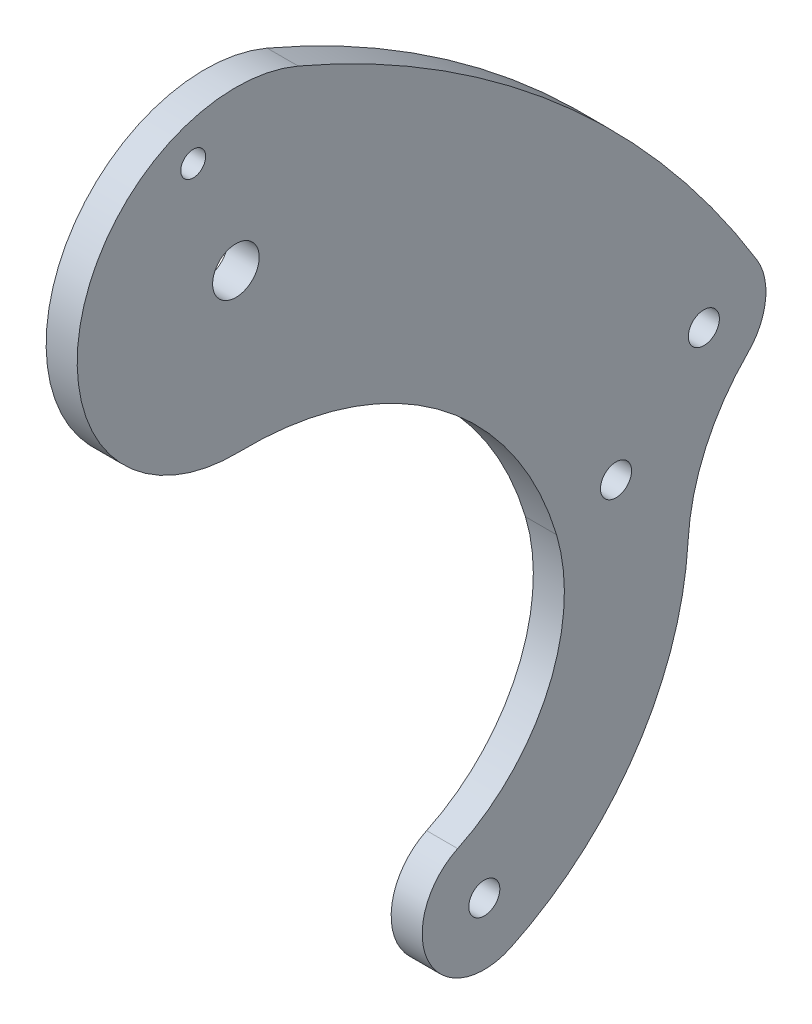
SolidWorks part; units mm, degrees
ref_plane "Front Plane" through (0, 0, 0) normal (0, 0, 1) x (1, 0, 0)
ref_plane "Top Plane" through (0, 0, 0) normal (0, 1, 0) x (1, 0, 0)
ref_plane "Right Plane" through (0, 0, 0) normal (1, 0, 0) x (0, 0, -1)
sketch "Sketch1" plane through (0, 0, 0) normal (1, 0, 0) x (0, 0, -1)
  line L0 (0, 0) -> (8.9803, 8.9803) construction
  line L1 (0, 0) -> (29.1581, 0) construction
  line L2 (8.9803, 8.9803) -> (17.9605, 17.9605) construction
  line L3 (0, 0) -> (-26.9408, -26.9408) construction
  line L4 (-26.9408, -51.0708) -> (-26.9408, -60.5958) construction
  line L5 (-26.9408, -26.9408) -> (-9.8783, -44.0033) construction
  line L6 (-9.8783, -44.0033) -> (-5.3882, -48.4934) construction
  line L7 (-5.3882, -48.4934) -> (47.3609, 4.2557) construction
  line L8 (-8.9803, 8.9803) -> (8.9803, 26.9408)
  line L9 (17.9605, 17.9605) -> (26.9408, 8.9803) construction
  circle A0 centre (0, 0) radius 3.175
  circle A1 centre (8.9803, 8.9803) radius 3.175 construction
  circle A2 centre (17.9605, 17.9605) radius 3.175
  circle A3 centre (-26.9408, -26.9408) radius 24.13 construction
  circle A4 centre (-26.9408, -60.5958) radius 3.175
  circle A5 centre (-26.9408, -26.9408) radius 6.35 construction
  arc A6 (26.9408, 8.9803) -> (8.9803, 26.9408) centre (17.9605, 17.9605) ccw
  arc A7 (-8.9803, 8.9803) -> (-12.1666, -3.6419) centre (0, 0) ccw
  arc A8 (-32.3874, -49.123) -> (-21.4941, -72.0685) centre (-26.9408, -60.5958) ccw
  arc A9 (-12.1666, -3.6419) -> (-32.3874, -49.123) centre (-48.7768, -14.6007) cw
  arc A10 (14.7335, -18.2518) -> (-21.4941, -72.0685) centre (-48.7768, -14.6007) cw
  arc A11 (26.9408, 8.9803) -> (14.7335, -18.2518) centre (56.5784, -20.6574) ccw
  dimension "D1" = 45
  dimension "D2" = 12.7
  dimension "D3" = 6.35
  dimension "D4" = 48.26
  dimension "D7" = 12.7
  dimension "D9" = 12.7
  dimension "D10" = 12.7
  dimension "D11" = 38.2152
  dimension "D5" = 38.1
  dimension "D6" = 9.525
  dimension "D8" = 6.35
extrude "Boss-Extrude1" add sketch "Sketch1" along normal blind 6.35
sketch "Sketch2" plane through (6.35, 0, 0) normal (1, 0, 0) x (0, 0, -1)
  line L0 (-9.0202, 98.7429) -> (-84.8371, 22.926) construction
  line L1 (8.9803, 26.9408) -> (-8.9803, 8.9803) construction
  line L2 (-8.9803, 8.9803) -> (8.9803, 26.9408) construction
  line L3 (-8.9803, 8.9803) -> (8.9803, 26.9408)
  circle A0 centre (-77.7408, 75.9292) radius 32.4611 construction
  arc A1 (-12.1666, -3.6419) -> (-76.9956, 43.4767) centre (-75.4787, -22.5936) ccw
  arc A2 (-32.3874, -49.123) -> (-12.1666, -3.6419) centre (-48.7768, -14.6007) ccw construction
  arc A3 (28.808, 24.5652) -> (-65.0005, 105.7857) centre (-144.7518, -81.1099) ccw
  arc A4 (26.9408, 8.9803) -> (8.9803, 26.9408) centre (17.9605, 17.9605) ccw construction
  arc A5 (-65.0005, 105.7857) -> (-76.9956, 43.4767) centre (-77.7408, 75.9292) ccw
  arc A6 (-8.9803, 8.9803) -> (-12.1666, -3.6419) centre (0, 0) ccw construction
  arc A7 (-8.9803, 8.9803) -> (-12.1666, -3.6419) centre (0, 0) ccw
  arc A8 (28.808, 24.5652) -> (8.9803, 26.9408) centre (17.9605, 17.9605) ccw
  circle A9 centre (-77.7408, 75.9292) radius 4.7625
  circle A11 centre (-86.4733, 99.2392) radius 2.54
  dimension "D2" = 5.08
  dimension "D4" = 203.2
  dimension "D5" = 9.525
  dimension "D7" = 23.31
  dimension "D8" = 24.892
  dimension "D1" = 63.5
  dimension "D3" = 50.8
  dimension "D6" = 136.525
extrude "Boss-Extrude2" add sketch "Sketch2" against normal up to surface (6.35 mm away) up to face at (0, -14.5423, 2.1881)
